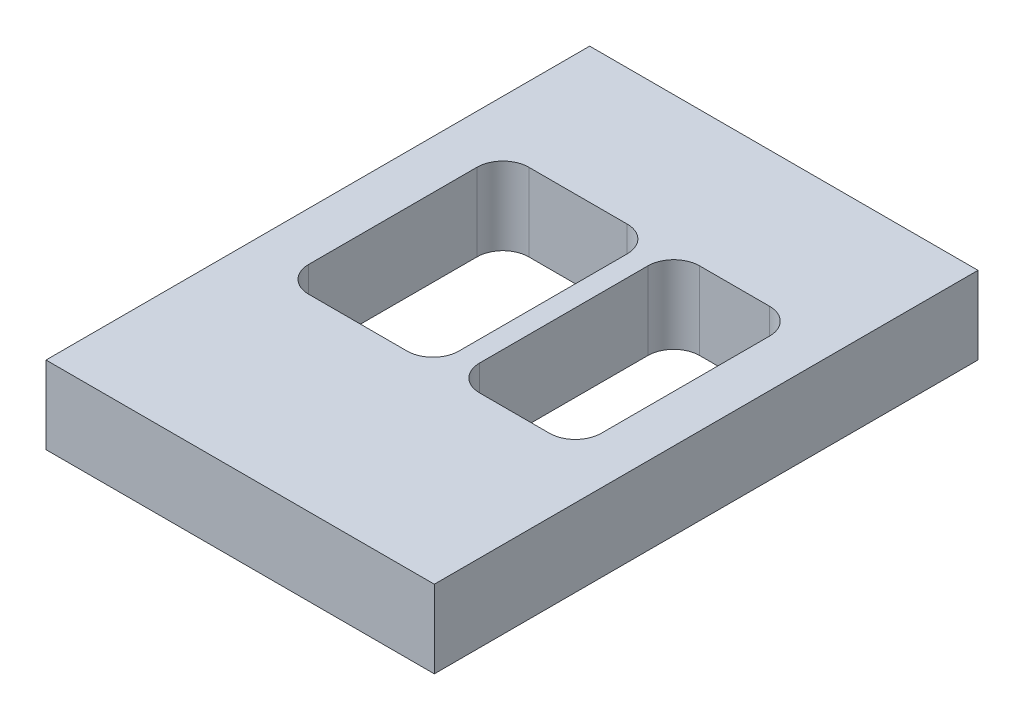
SolidWorks part; units mm, degrees
material "K110"
ref_plane "Front Plane" through (0, 0, 0) normal (0, 0, 1) x (1, 0, 0)
ref_plane "Top Plane" through (0, 0, 0) normal (0, 1, 0) x (1, 0, 0)
ref_plane "Right Plane" through (0, 0, 0) normal (1, 0, 0) x (0, 0, -1)
sketch "Sketch1" plane through (0, 0, 0) normal (0, 1, 0) x (1, 0, 0)
  line L1 (-75, 105) -> (75, 105)
  line L2 (-75, 105) -> (-75, -105)
  line L3 (-75, -105) -> (75, -105)
  line L4 (75, 105) -> (75, -105)
  line L5 (-75, 105) -> (75, -105) construction
  line L6 (-75, -105) -> (75, 105) construction
  point P0 (0, 0)
  dimension "D1" = 210
  dimension "D2" = 150
extrude "Boss-Extrude1" add sketch "Sketch1" against normal blind 30
sketch "Sketch2" plane through (0, 0, 0) normal (0, 1, 0) x (1, 0, 0)
  line L0 (24.75, 42.73) -> (40.88, 42.73) construction
  line L1 (40.88, 42.73) -> (40.88, -22.27) construction
  line L2 (40.88, -22.27) -> (24.75, -22.27) construction
  line L3 (24.75, -22.27) -> (24.75, -11.27) construction
  line L4 (27.75, -8.27) -> (33.88, -8.27) construction
  line L5 (35.88, -6.27) -> (35.88, 11.73) construction
  line L6 (33.88, 13.73) -> (27.75, 13.73) construction
  line L7 (24.75, 42.73) -> (24.75, 16.73) construction
  line L8 (-35.37, 42.73) -> (-13.25, 42.73) construction
  line L9 (-13.25, 42.73) -> (-13.25, 34.23) construction
  line L10 (-14.75, 32.73) -> (-29.37, 32.73) construction
  line L11 (-35.37, 26.73) -> (-35.37, -6.27) construction
  line L12 (-29.37, -12.27) -> (-14.75, -12.27) construction
  line L13 (-13.25, -22.27) -> (-13.25, -13.77) construction
  line L14 (-35.37, -22.27) -> (-13.25, -22.27) construction
  line L15 (-40.37, 37.73) -> (-40.37, -17.27) construction
  line L16 (24.75, 42.73) -> (40.88, 42.73)
  line L17 (40.88, 42.73) -> (40.88, -22.27)
  line L18 (40.88, -22.27) -> (24.75, -22.27)
  line L19 (24.75, -22.27) -> (24.75, -11.27)
  line L20 (27.75, -8.27) -> (33.88, -8.27)
  line L21 (35.88, -6.27) -> (35.88, 11.73)
  line L22 (33.88, 13.73) -> (27.75, 13.73)
  line L23 (24.75, 42.73) -> (24.75, 16.73)
  line L24 (-35.37, 42.73) -> (-13.25, 42.73)
  line L25 (-13.25, 42.73) -> (-13.25, 34.23)
  line L26 (-14.75, 32.73) -> (-29.37, 32.73)
  line L27 (-35.37, 26.73) -> (-35.37, -6.27)
  line L28 (-29.37, -12.27) -> (-14.75, -12.27)
  line L29 (-13.25, -22.27) -> (-13.25, -13.77)
  line L30 (-35.37, -22.27) -> (-13.25, -22.27)
  line L31 (-40.37, 37.73) -> (-40.37, -17.27)
  arc A0 (27.75, -8.27) -> (24.75, -11.27) centre (27.75, -11.27) ccw construction
  arc A1 (33.88, -8.27) -> (35.88, -6.27) centre (33.88, -6.27) ccw construction
  arc A2 (35.88, 11.73) -> (33.88, 13.73) centre (33.88, 11.73) ccw construction
  arc A3 (24.75, 16.73) -> (27.75, 13.73) centre (27.75, 16.73) ccw construction
  arc A4 (-35.37, 42.73) -> (-40.37, 37.73) centre (-35.37, 37.73) ccw construction
  arc A5 (-14.75, 32.73) -> (-13.25, 34.23) centre (-14.75, 34.23) ccw construction
  arc A6 (-29.37, 32.73) -> (-35.37, 26.73) centre (-29.37, 26.73) ccw construction
  arc A7 (-35.37, -6.27) -> (-29.37, -12.27) centre (-29.37, -6.27) ccw construction
  arc A8 (-13.25, -13.77) -> (-14.75, -12.27) centre (-14.75, -13.77) ccw construction
  arc A9 (-40.37, -17.27) -> (-35.37, -22.27) centre (-35.37, -17.27) ccw construction
  arc A10 (27.75, -8.27) -> (24.75, -11.27) centre (27.75, -11.27) ccw
  arc A11 (33.88, -8.27) -> (35.88, -6.27) centre (33.88, -6.27) ccw
  arc A12 (35.88, 11.73) -> (33.88, 13.73) centre (33.88, 11.73) ccw
  arc A13 (24.75, 16.73) -> (27.75, 13.73) centre (27.75, 16.73) ccw
  arc A14 (-35.37, 42.73) -> (-40.37, 37.73) centre (-35.37, 37.73) ccw
  arc A15 (-14.75, 32.73) -> (-13.25, 34.23) centre (-14.75, 34.23) ccw
  arc A16 (-29.37, 32.73) -> (-35.37, 26.73) centre (-29.37, 26.73) ccw
  arc A17 (-35.37, -6.27) -> (-29.37, -12.27) centre (-29.37, -6.27) ccw
  arc A18 (-13.25, -13.77) -> (-14.75, -12.27) centre (-14.75, -13.77) ccw
  arc A19 (-40.37, -17.27) -> (-35.37, -22.27) centre (-35.37, -17.27) ccw
sketch "Sketch3" plane through (0, 0, 0) normal (0, 1, 0) x (1, 0, 0)
  line L1 (-56.25, 52.73) -> (1.75, 52.73)
  line L2 (-56.25, 52.73) -> (-56.25, -32.27)
  line L3 (-56.25, -32.27) -> (1.75, -32.27)
  line L4 (1.75, 52.73) -> (1.75, -32.27)
  line L5 (9.75, 52.73) -> (56.75, 52.73)
  line L6 (9.75, 52.73) -> (9.75, -32.27)
  line L7 (9.75, -32.27) -> (56.75, -32.27)
  line L8 (56.75, 52.73) -> (56.75, -32.27)
  line L15 (24.75, 42.73) -> (24.75, 16.73) construction
  line L16 (-13.25, 42.73) -> (-13.25, 34.23) construction
  line L20 (40.88, 10.23) -> (56.75, 10.23) construction
  line L22 (40.88, 42.73) -> (40.88, -22.27) construction
  point P32 (0, 0)
  point P33 (0, 0)
  point P34 (0, 0)
  dimension "D1" = 85
  dimension "D4" = 15
  dimension "D5" = 15
  dimension "D6" = 47
  dimension "D7" = 58
extrude "Cut-Extrude1" cut sketch "Sketch3" against normal up to next
fillet "Fillet1" radius 10 8 edges at (9.75, -15, -52.73) (56.75, -15, 32.27) (56.75, -15, -52.73) (9.75, -15, 32.27) (-56.25, -15, 32.27) (1.75, -15, 32.27) (1.75, -15, -52.73) (-56.25, -15, -52.73)
